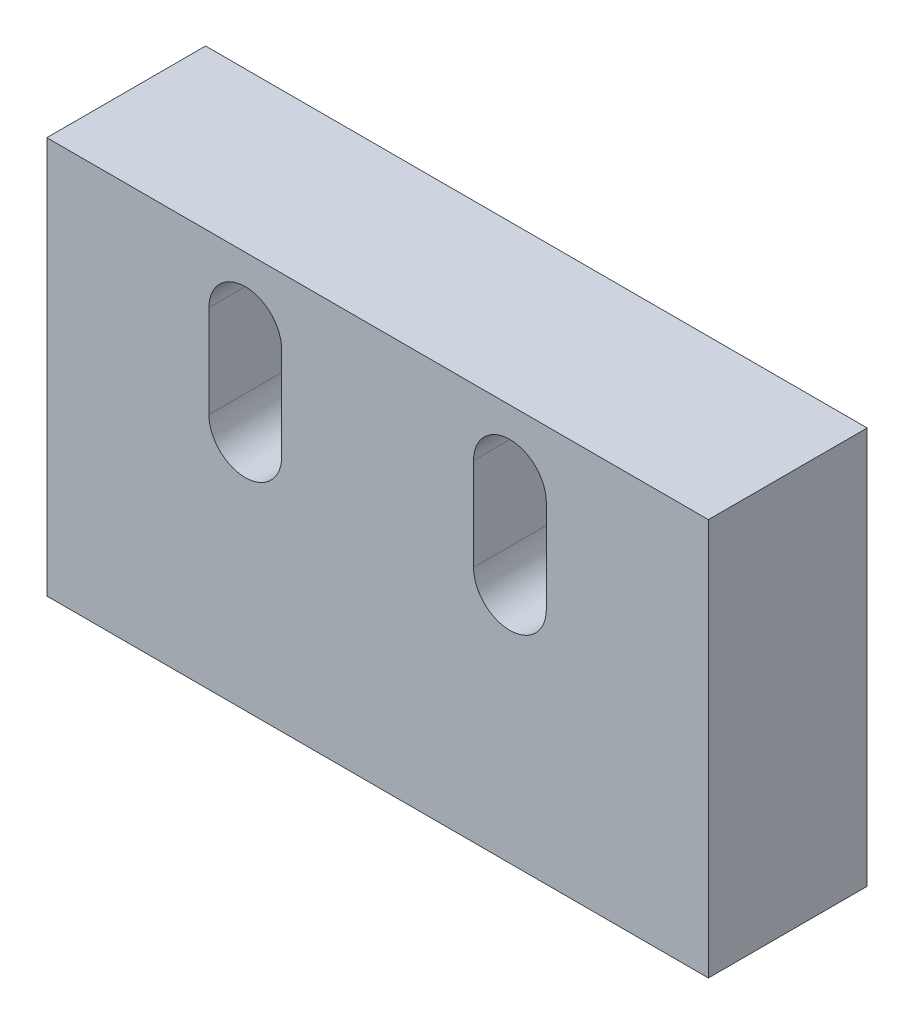
SolidWorks part; units mm, degrees
ref_plane "Front Plane" through (0, 0, 0) normal (0, 0, 1) x (1, 0, 0)
ref_plane "Top Plane" through (0, 0, 0) normal (0, 1, 0) x (1, 0, 0)
ref_plane "Right Plane" through (0, 0, 0) normal (1, 0, 0) x (0, 0, -1)
sketch "Sketch1" plane through (0, 0, 0) normal (0, 0, 1) x (1, 0, 0)
  line L1 (-25, -15) -> (25, -15)
  line L2 (-25, -15) -> (-25, 15)
  line L3 (-25, 15) -> (25, 15)
  line L4 (25, -15) -> (25, 15)
  line L5 (-25, -15) -> (25, 15) construction
  line L6 (-25, 15) -> (25, -15) construction
  point P0 (0, 0)
  dimension "D1" = 50
  dimension "D2" = 30
extrude "Boss-Extrude1" add sketch "Sketch1" along normal mid plane 12
hole_wizard "M5 Clearance Slot1" positions "Sketch3" profile "Sketch4" size "M5" standard "ANSI Metric" slot yes end condition through all
sketch "Sketch3" plane through (0, 0, 6) normal (0, 0, 1) x (1, 0, 0)
  line L0 (-10, 12.75) -> (-10, 0.25) construction
  line L1 (-25, 15) -> (-25, -15) construction
  line L2 (25, 15) -> (-25, 15) construction
  point P0 (-10, 6.5)
  point P4 (10, 6.5)
  point P9 (0, 0)
  dimension "D1" = 12.5
  dimension "D2" = 15
  dimension "D3" = 2.25
  dimension "D4" = 20
sketch "Sketch4" plane through (-10, 6.5, 6) normal (1, 0, 0) x (0, -1, 0)
  line L0 (0, 0) -> (0, 12)
  line L1 (0, 12) -> (2.75, 12)
  line L2 (2.75, 12) -> (2.75, 0)
  line L5 (2.75, 0) -> (0, 0)
  line L11 (0, -6.35) -> (0, 107.95) construction
  dimension "Thru Hole Dia." = 5.5
  dimension "Thru Hole Depth" = 12
hole_wizard "M5x0.8 Tapped Hole1" positions "Sketch6" profile "Sketch5" tap size "M5x0.8" standard "ANSI Metric"
sketch "Sketch6" plane through (0, -15, 0) normal (0, -1, 0) x (-1, 0, 0)
  line L0 (0, 0) -> (43.2043, 0) construction
  line L2 (-25, -6) -> (-25, 6) construction
  point P0 (-15, 0)
  dimension "D1" = 10
sketch "Sketch5" plane through (15, -15, 0) normal (1, 0, 0) x (0, 0, -1)
  line L0 (0, 0) -> (0, 8.4)
  line L1 (0, 8.4) -> (2.1, 7.1382)
  line L2 (2.1, 7.1382) -> (2.1, 0)
  line L5 (2.1, 0) -> (0, 0)
  line L10 (0, 8.4) -> (-2.1, 7.1382) construction
  line L11 (0, -6.35) -> (0, 107.95) construction
  dimension "Tap Drill Dia." = 4.2
  dimension "Tap Drill Depth" = 8.4
  dimension "Drill Angle" = 118
cosmetic thread "Hole Thread1" parameters "D1"=6, "D2"=5
mirror "Mirror1" about plane through (0, 0, 0) normal (1, 0, 0) of "M5x0.8 Tapped Hole1"
cosmetic thread "Hole Thread2" parameters "D1"=6, "D2"=5
